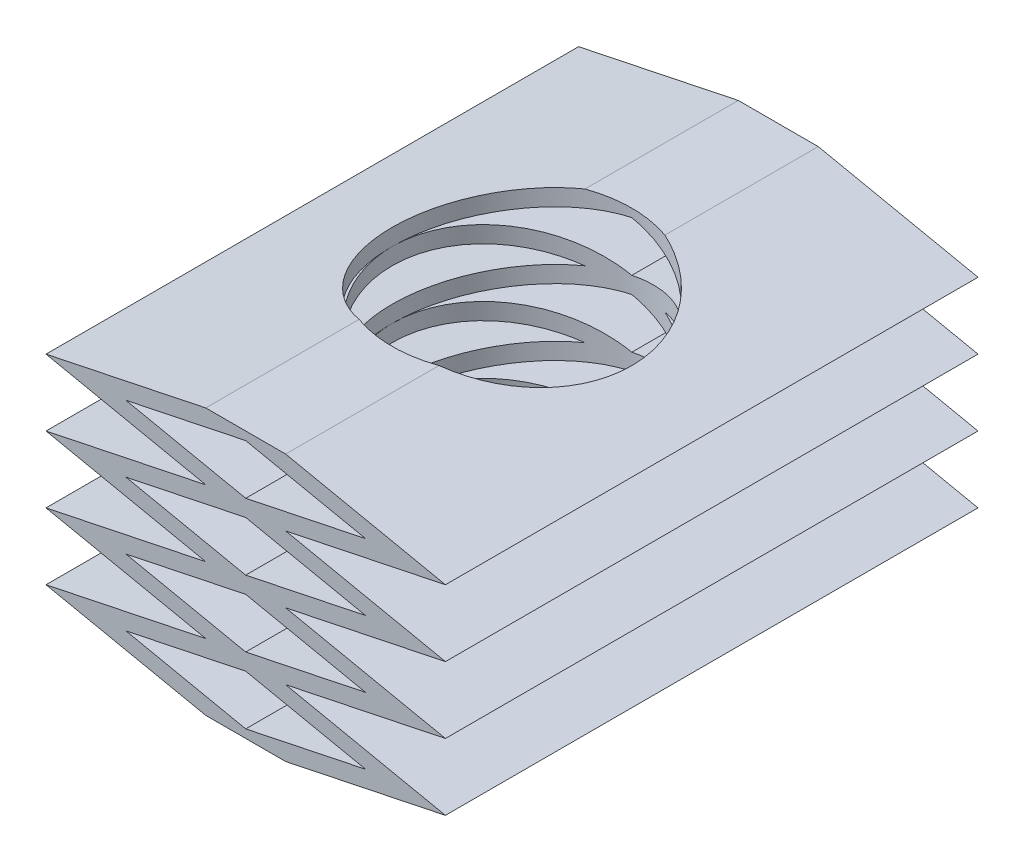
SolidWorks part; units mm, degrees
material "ABS"
ref_plane "Front Plane" through (0, 0, 0) normal (0, 0, 1) x (1, 0, 0)
ref_plane "Top Plane" through (0, 0, 0) normal (0, 1, 0) x (1, 0, 0)
ref_plane "Right Plane" through (0, 0, 0) normal (1, 0, 0) x (0, 0, -1)
sketch "Sketch1" plane through (0, 0, 0) normal (0, 0, 1) x (1, 0, 0)
  line L0 (0, 0) -> (4, 1.25)
  line L1 (4, 1.25) -> (0, 2.5)
  line L2 (0, 2.5) -> (1, 2.5)
  line L3 (1, 2.5) -> (5, 1.25)
  line L4 (5, 1.25) -> (1, 0)
  line L5 (1, 0) -> (0, 0)
  line L6 (5, 1.25) -> (4, 1.25) construction
  line L7 (0, 2.5) -> (0, 0) construction
  line L8 (5, 1.25) -> (0, 1.25) construction
  line L9 (2.5, 1.25) -> (2.5, 0.4687) construction
  line L10 (4, 0) -> (5, 0)
  line L11 (5, 0) -> (1, 1.25)
  line L12 (0, 1.25) -> (4, 0)
  line L13 (5, 2.5) -> (4, 2.5)
  line L14 (4, 2.5) -> (0, 1.25)
  line L15 (1, 1.25) -> (5, 2.5)
  line L16 (4, 5) -> (5, 5)
  line L17 (1, 5) -> (0, 5)
  line L18 (5, 3.75) -> (1, 5)
  line L19 (0, 5) -> (4, 3.75)
  line L20 (0, 3.75) -> (4, 5)
  line L21 (5, 5) -> (1, 3.75)
  line L22 (4, 3.75) -> (0, 2.5)
  line L23 (1, 2.5) -> (5, 3.75)
  line L24 (4, 2.5) -> (0, 3.75)
  line L25 (1, 3.75) -> (5, 2.5)
  dimension "D2" = 2.5
  dimension "D3" = 5
  dimension "D1" = 1
extrude "Boss-Extrude2" [suppressed] add sketch "Sketch1" along normal blind 5 contours L4 L12 L10 L11 | L15 L1 L0 L11 L4 L3 | L0 L12 L4 L11 | L12 L0 L5 L4 | L11 L15 L1 L14 L12 L0 | L1 L15 L3 L14 | L3 L15 L13 L14 | L14 L3 L2 L1 | L25 L23 L24 L13 | L23 L24 L22 L2 | L25 L22 L24 L23 | L25 L21 L19 L20 L24 L22 | L22 L25 L23 L18 L21 L19 | L21 L18 L20 L19 | L19 L20 L18 L17 | L21 L16 L20 L18
sketch "Sketch2" plane through (0, 0, 0) normal (0, 0, 1) x (1, 0, 0)
  line L0 (-0.75, 0) -> (0.75, 0)
  line L1 (0, 0) -> (0, 0.625) construction
  line L2 (0.75, 0) -> (3.75, 0.625)
  line L3 (3.75, 0.625) -> (0, 0.625) construction
  line L4 (-0.75, 0) -> (-3.75, 0.625)
  line L5 (-0.75, 1.25) -> (0.75, 1.25)
  line L6 (0.75, 1.25) -> (3.75, 0.625)
  line L7 (-0.75, 1.25) -> (-3.75, 0.625)
  line L8 (0.75, 0) -> (-0.75, 0)
  line L9 (-0.75, 0) -> (2.25, 0.625)
  line L10 (0.75, 0) -> (-2.25, 0.625)
  line L11 (-0.75, 1.25) -> (2.25, 0.625)
  line L12 (0.75, 1.25) -> (-0.75, 1.25)
  line L13 (0.75, 1.25) -> (-2.25, 0.625)
  point P13 (0, 0)
  dimension "D1" = 1.5
  dimension "D3" = 7.5
  dimension "D4" = 1.25
extrude "Boss-Extrude3" add sketch "Sketch2" along normal blind 10 contours L13 L11 L7 L4 L9 L10 | L6 L13 L11 L9 L10 L2 | L13 L5 L11 | L0 L10 L9 region at (0, 0.0521, 0) region at (-2.2419, 0.3512, 0) region at (0.3831, 0.1168, 0) region at (0, 1.1979, 0)
pattern_linear "LPattern1" count 4 spacing 1.25 along (0, 1, 0) of "Boss-Extrude3"
sketch "Sketch3" plane through (0, 0, 0) normal (0, -1, 0) x (1, 0, 0)
  line L0 (0, 0) -> (0, 10) construction
  line L1 (-0.75, 10) -> (0.75, 10) construction
  circle A0 centre (0, 5) radius 2.25
  dimension "D1" = 4.5
extrude "Cut-Extrude1" cut sketch "Sketch3" against normal through all
